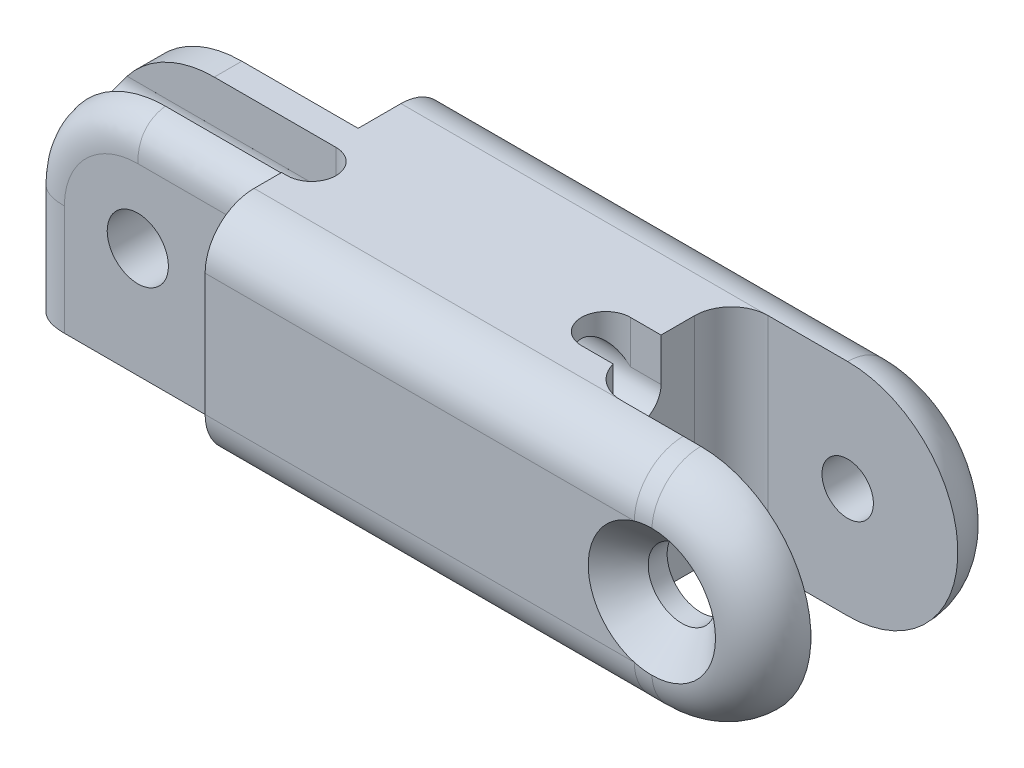
SolidWorks part; units mm, degrees
ref_plane "Front Plane" through (0, 0, 0) normal (0, 0, 1) x (1, 0, 0)
ref_plane "Top Plane" through (0, 0, 0) normal (0, 1, 0) x (1, 0, 0)
ref_plane "Right Plane" through (0, 0, 0) normal (1, 0, 0) x (0, 0, -1)
sketch "Sketch2" plane through (0, 0, 0) normal (0, 1, 0) x (1, 0, 0)
  line L0 (-13.5, 10) -> (32, 10)
  line L1 (32, 10) -> (32, 6)
  line L2 (32, 6) -> (16.5, 6)
  line L3 (13.5, 3) -> (13.5, -3)
  line L4 (16.5, -6) -> (32, -6)
  line L5 (32, -6) -> (32, -10)
  line L7 (-32, -6) -> (-32, 2.5)
  line L8 (-49.3622, 0) -> (56.3776, 0) construction
  line L9 (0, 21.2372) -> (0, -19.0689) construction
  line L10 (13.5, 3) -> (16.5, 3) construction
  line L11 (16.5, 3) -> (16.5, 6) construction
  line L16 (-13.5, -10) -> (32, -10)
  line L18 (-32, -6) -> (-13.5, -6)
  line L19 (-13.5, -6) -> (-13.5, -10)
  line L20 (-32, 2.5) -> (-13.5, 2.5)
  line L21 (-13.5, 2.5) -> (-13.5, 10)
  arc A0 (16.5, 6) -> (13.5, 3) centre (16.5, 3) ccw
  arc A1 (16.5, -6) -> (13.5, -3) centre (16.5, -3) cw
  point P13 (16.5, 3)
  dimension "D1" = 64
  dimension "D2" = 20
  dimension "D3" = 4
  dimension "D4" = 18.5
  dimension "D5" = 12
  dimension "D6" = 3
  dimension "D7" = 3
  dimension "D8" = 7.5
  dimension "D9" = 4
  dimension "D10" = 8.5
  dimension "D11" = 18.5
extrude "Boss-Extrude1" add sketch "Sketch2" along normal blind 18
sketch "Sketch5" plane through (0, 0, 10) normal (0, 0, 1) x (1, 0, 0)
  line L0 (-32, 9) -> (31.8491, 9) construction
  line L1 (-23, 18) -> (-23, 0) construction
  line L2 (32, 18) -> (32, 0) construction
  line L3 (-13.5, 18) -> (32, 18) construction
  line L4 (23, 18) -> (23, 0) construction
  line L5 (-32, 18) -> (-32, 0) construction
  line L6 (-32, 9) -> (-32, 0)
  line L7 (-32, 18) -> (-13.5, 18) construction
  line L8 (-32, 0) -> (23, 0)
  line L9 (-23, 18) -> (23, 18)
  arc A0 (-23, 18) -> (-32, 9) centre (-23, 9) ccw
  arc A1 (23, 0) -> (23, 18) centre (23, 9) ccw
  circle A2 centre (-23, 9) radius 2.5
  dimension "D2" = 5
  dimension "D1" = 9
extrude "Cut-Extrude1" cut sketch "Sketch5" against normal blind 20 flip side to cut
sketch "Sketch6" plane through (0, 0, 10) normal (0, 0, 1) x (1, 0, 0)
  line L0 (23, 0) -> (23, 18) construction
  point P4 (23, 9)
hole_wizard "CSK for M5 Countersunk Flat Head Screw1" positions "Sketch7" profile "Sketch8" countersink size "M5" standard "DIN" end condition up to next
sketch "Sketch7" plane through (0, 0, 10) normal (0, 0, 1) x (1, 0, 0)
  point P0 (23, 9)
sketch "Sketch8" plane through (23, 9, 10) normal (1, 0, 0) x (0, -1, 0)
  line L0 (0, 0) -> (0, 4)
  line L1 (0, 4) -> (2.75, 4)
  line L2 (2.75, 4) -> (2.75, 2.45)
  line L3 (2.75, 2.45) -> (5.2, 0)
  line L5 (5.2, 0) -> (0, 0)
  line L6 (-2.75, 2.45) -> (-5.2, 0) construction
  line L11 (0, -6.35) -> (0, 107.95) construction
  dimension "Thru Hole Dia." = 5.5
  dimension "Thru Hole Depth" = 4
  dimension "Near C'Sink Dia." = 10.4
  dimension "Near C'Sink Angle" = 90
hole_wizard "M5 Tapped Hole1" positions "Sketch9" profile "Sketch11" tap size "M5" standard "DIN" end condition through all
sketch "Sketch9" plane through (0, 0, 10) normal (0, 0, 1) x (1, 0, 0)
  point P0 (23, 9)
sketch "Sketch11" plane through (23, 9, 10) normal (1, 0, 0) x (0, -1, 0)
  line L0 (0, 0) -> (0, 20)
  line L1 (0, 20) -> (2.1, 20)
  line L2 (2.1, 20) -> (2.1, 3.1)
  line L3 (2.1, 3.1) -> (5.2, 0)
  line L5 (5.2, 0) -> (0, 0)
  line L6 (-2.1, 3.1) -> (-5.2, 0) construction
  line L11 (0, -6.35) -> (0, 107.95) construction
  dimension "Thru Tap Drill Dia." = 4.2
  dimension "Thru Tap Drill Depth" = 20
  dimension "Near C'Sink Dia." = 10.4
  dimension "Near C'Sink Angle" = 90
cosmetic thread "Hole Thread1" parameters "D2"=5
fillet "Fillet1" radius 4 2 edges at (4.75, 0, 10) (4.75, 18, 10)
fillet "Fillet2" radius 4 3 edges at (4.75, 0, -10) (32, 9, -10) (4.75, 18, -10)
fillet "Fillet3" radius 3 3 edges at (-32, 4.5, 6) (-18.25, 18, 6) (-29.364, 15.364, 6) conic rho 0.5
sketch "Sketch13" plane through (13.5, 0, 0) normal (1, 0, 0) x (0, 0, -1)
  line L0 (-1.75, 21.4915) -> (-1.75, -4.5302) construction
  line L1 (-3, 18) -> (3, 18) construction
  circle A0 centre (-1.75, 14.5) radius 2
  dimension "D2" = 4
  dimension "D3" = 3.5
  dimension "D1" = 1.75
extrude "Cut-Extrude2" cut sketch "Sketch13" against normal through all both and the other way through all
sketch "Sketch14" plane through (0, 18, 0) normal (0, 1, 0) x (1, 0, 0)
  line L0 (-30.1236, 0.2504) -> (-13.0557, 0.2504)
  line L1 (-30.0557, -3.75) -> (-13.0557, -3.75)
  line L3 (-30.0557, -3.75) -> (-30.1236, 0.2504)
  arc A0 (-13.0557, -3.75) -> (-13.0557, 0.2504) centre (-13.0557, -1.7498) ccw
  spline S1 degree 3 poles (-28.5797, -3) (-28.4473, -2.8693) (-28.3242, -2.7233) (-28.1669, -2.4679) (-28.12, -2.3776) (-28.0431, -2.1872) (-28.0127, -2.0851) (-27.9764, -1.8774) (-27.9703, -1.7698) (-27.9841, -1.5572) (-28.0036, -1.4537) (-28.0944, -1.1509) (-28.1934, -0.9724) (-28.4222, -0.6565) (-28.5506, -0.5207) (-28.8219, -0.2789) (-28.9619, -0.1762) (-29.3834, 0.0849) (-29.6717, 0.1991) (-30.0706, 0.2557) (-30.2006, 0.2556) (-30.4459, 0.209) (-30.5594, 0.1634) (-30.769, 0.0188) (-30.8624, -0.0793) (-31.0226, -0.3256) (-31.0911, -0.4779) (-31.1703, -0.7331) (-31.1932, -0.8231) (-31.2322, -1.0133) (-31.2481, -1.1133) (-31.2724, -1.3157) (-31.281, -1.419) (-31.2912, -1.6301) (-31.2926, -1.7379) (-31.2863, -2.055) (-31.2677, -2.2665) (-31.2021, -2.6575) (-31.1546, -2.8399) (-31.0922, -3) knots 0 0 0 0 0.0625 0.0625 0.09375 0.09375 0.125 0.125 0.15625 0.15625 0.1875 0.1875 0.25 0.25 0.3125 0.3125 0.375 0.375 0.5 0.5 0.5625 0.5625 0.625 0.625 0.6875 0.6875 0.75 0.75 0.78125 0.78125 0.8125 0.8125 0.84375 0.84375 0.875 0.875 0.9375 0.9375 1 1 1 1 construction
  spline S2 degree 3 poles (-31.0922, -3) (-31.0381, -3.1387) (-30.9701, -3.2552) (-30.8108, -3.4526) (-30.7195, -3.5323) (-30.5254, -3.6532) (-30.4205, -3.6957) (-30.205, -3.7461) (-30.094, -3.7546) (-29.7507, -3.7337) (-29.5173, -3.6588) (-29.0422, -3.4019) (-28.8092, -3.2263) (-28.5797, -3) knots 0 0 0 0 0.125 0.125 0.25 0.25 0.375 0.375 0.5 0.5 0.75 0.75 1 1 1 1 construction
  dimension "D2" = 2.0002
  dimension "D1" = 17
extrude "Cut-Extrude3" cut sketch "Sketch14" against normal blind 3.5
sketch "Sketch15" plane through (0, 18, 0) normal (0, 1, 0) x (1, 0, 0)
sketch "Sketch16" plane through (0, 18, 0) normal (0, 1, 0) x (1, 0, 0)
  line L0 (-8.0769, -1.75) -> (29.6251, -1.75) construction
  line L1 (11, 0.25) -> (19.0559, 0.25)
  line L3 (11, -3.75) -> (19.0559, -3.75)
  line L4 (19.0559, 0.25) -> (19.0559, -3.75)
  line L5 (13.5, -3) -> (13.5, 3) construction
  arc A0 (11, 0.25) -> (11, -3.75) centre (11, -1.75) ccw
  dimension "D2" = 4
  dimension "D1" = 1.75
  dimension "D3" = 2.5
extrude "Cut-Extrude4" cut sketch "Sketch16" against normal blind 3.5
